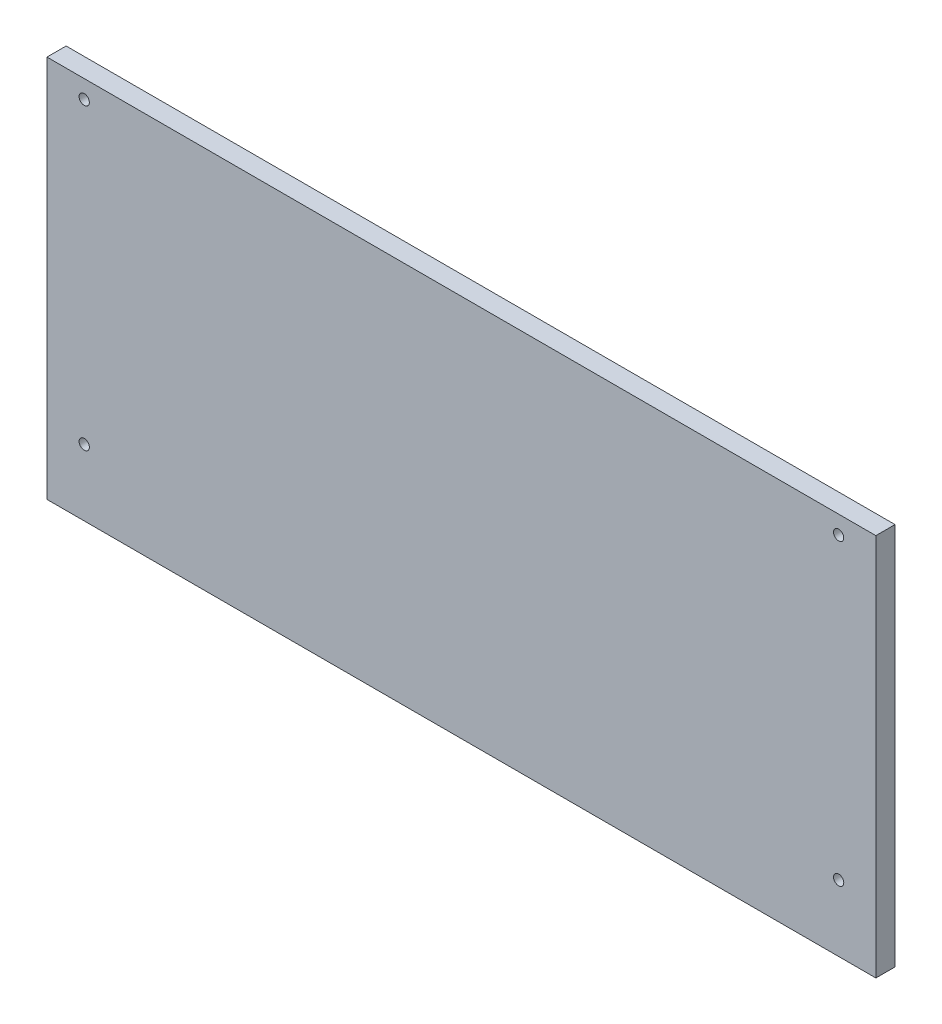
SolidWorks part; units mm, degrees
material "Acrylic (Medium-high impact)"
ref_plane "Front Plane" through (0, 0, 0) normal (0, 0, 1) x (1, 0, 0)
ref_plane "Top Plane" through (0, 0, 0) normal (0, 1, 0) x (1, 0, 0)
ref_plane "Right Plane" through (0, 0, 0) normal (1, 0, 0) x (0, 0, -1)
sketch "Sketch1" plane through (0, 0, 0) normal (0, 0, 1) x (1, 0, 0)
  line L1 (274.7772, 127) -> (0, 127)
  line L2 (274.7772, 127) -> (274.7772, 0)
  line L3 (274.7772, 0) -> (0, 0)
  line L4 (0, 127) -> (0, 0)
  line L5 (274.7772, 127) -> (0, 0) construction
  line L6 (274.7772, 0) -> (0, 127) construction
  point P0 (137.3886, 63.5)
  dimension "D1" = 127
  dimension "D2" = 274.7772
extrude "Boss-Extrude1" add sketch "Sketch1" along normal blind 6.35
hole_wizard "M3 Clearance Hole1" positions "Sketch2" profile "Sketch3" hole size "M3" standard "ANSI Metric" end condition through all
sketch "Sketch2" plane through (0, 0, 6.35) normal (0, 0, 1) x (1, 0, 0)
  line L0 (0, 127) -> (0, 0) construction
  line L1 (274.7772, 127) -> (0, 127) construction
  line L2 (274.7772, 0) -> (274.7772, 127) construction
  line L3 (0, 0) -> (274.7772, 0) construction
  point P0 (12.3444, 121.0056)
  point P2 (12.3444, 21.9964)
  point P4 (262.4328, 21.9964)
  point P6 (262.4328, 121.0056)
  dimension "D1" = 12.3444
  dimension "D2" = 5.9944
  dimension "D3" = 12.3444
  dimension "D4" = 21.9964
sketch "Sketch3" plane through (12.3444, 121.0056, 6.35) normal (1, 0, 0) x (0, -1, 0)
  line L0 (0, 0) -> (0, 6.35)
  line L1 (0, 6.35) -> (1.7, 6.35)
  line L2 (1.7, 6.35) -> (1.7, 0)
  line L5 (1.7, 0) -> (0, 0)
  line L11 (0, -6.35) -> (0, 107.95) construction
  dimension "Thru Hole Dia." = 3.4
  dimension "Thru Hole Depth" = 6.35
sketch "Sketch4" plane through (0, 0, 6.35) normal (0, 0, 1) x (1, 0, 0)
  line L0 (0, 127) -> (0, 0) construction
  line L1 (46.99, 107.95) -> (50.4952, 107.95)
  line L2 (46.99, 107.95) -> (46.99, 31.75)
  line L3 (46.99, 31.75) -> (50.4952, 31.75)
  line L4 (50.4952, 107.95) -> (50.4952, 31.75)
  line L5 (224.282, 107.95) -> (227.7872, 107.95)
  line L6 (224.282, 107.95) -> (224.282, 31.75)
  line L7 (224.282, 31.75) -> (227.7872, 31.75)
  line L8 (227.7872, 107.95) -> (227.7872, 31.75)
  line L9 (274.7772, 0) -> (274.7772, 127) construction
  line L10 (274.7772, 127) -> (0, 127) construction
  dimension "D1" = 3.5052
  dimension "D2" = 76.2
  dimension "D3" = 46.99
  dimension "D4" = 46.99
  dimension "D5" = 19.05
extrude "Cut-Extrude1" [suppressed] cut sketch "Sketch4" against normal through all
sketch "Sketch5" plane through (0, 0, 6.35) normal (0, 0, 1) x (1, 0, 0)
  line L0 (0, 0) -> (274.7772, 0)
  line L1 (274.7772, 0) -> (274.7772, 38.6174)
  line L2 (274.7772, 0) -> (274.7772, 127) construction
  line L3 (274.7772, 38.6174) -> (0, 0)
  dimension "D1" = 8
extrude "Cut-Extrude2" [suppressed] cut sketch "Sketch5" against normal through all
